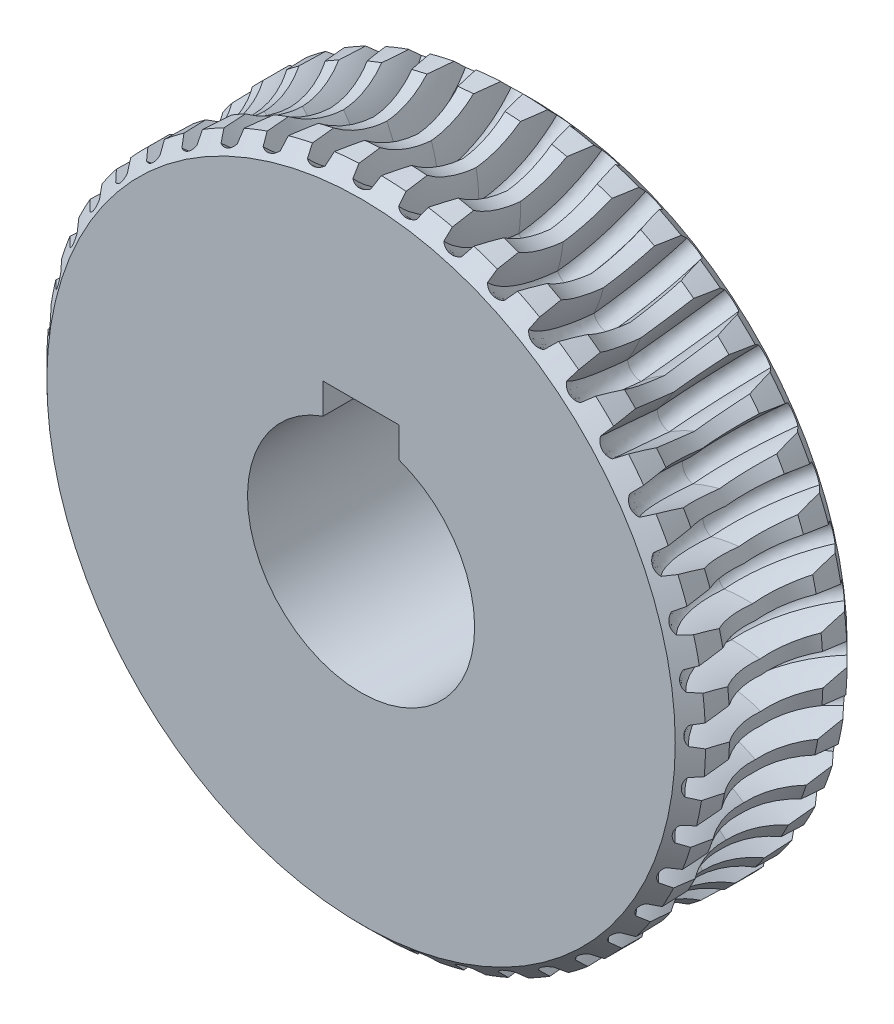
SolidWorks part; units mm, degrees
note: The reader was unsure of these and kept them because the rebuilt part matched: shared geometry of "Sketch4<2>".
ref_plane "Front Plane" through (0, 0, 0) normal (0, 0, 1) x (1, 0, 0)
ref_plane "Top Plane" through (0, 0, 0) normal (0, 1, 0) x (1, 0, 0)
ref_plane "Right Plane" through (0, 0, 0) normal (1, 0, 0) x (0, 0, -1)
sketch "Sketch1" plane through (0, 0, 0) normal (0, 0, 1) x (1, 0, 0)
  line L0 (0, 0) -> (0, 55.6872) construction
  line L2 (-5, 18.1421) -> (5, 18.1421)
  line L3 (-5, 18.1421) -> (-5, 14.1421)
  line L5 (5, 18.1421) -> (5, 14.1421)
  line L6 (-5, 18.1421) -> (0, 15) construction
  line L7 (0, 15) -> (5, 18.1421) construction
  circle A0 centre (0, 0) radius 43.5
  arc A1 (-5, 14.1421) -> (5, 14.1421) centre (0, 0) ccw
  point P4 (0, 15)
  dimension "D1" = 87
  dimension "D2" = 30
  dimension "D3" = 10
  dimension "D4" = 4
extrude "Boss-Extrude1" add sketch "Sketch1" along normal mid plane 22.7
chamfer "Chamfer1" distance 2 angle 45 2 edges at (43.5, 0, -11.35) (43.5, 0, 11.35)
sketch "Sketch2" plane through (0, 0, 0) normal (1, 0, 0) x (0, 0, -1)
  line L0 (0, 0) -> (0, -52) construction
  line L1 (0, 0) -> (54.4934, 0) construction
  circle A0 centre (0, -52) radius 10.5
  dimension "D2" = 21
  dimension "D1" = 52
revolve "Cut-Revolve1" cut sketch "Sketch2" angle 360 about L1
sketch "Sketch3" plane through (0, 0, 0) normal (1, 0, 0) x (0, 0, -1)
  circle A1 centre (0, -52) radius 10.5
  circle A2 centre (0, -52) radius 10.5
  dimension "D1" = 0
curve "Helix/Spiral1" pitch 6 height 1.5 turns 0.25
sketch "Sketch4" plane through (0, 0, 0) normal (0, 0, 1) x (1, 0, 0)
  line L0 (0, 0) -> (0, -56.2527) construction
  line L1 (3.45, -45.44) -> (-3.45, -45.44)
  line L2 (-3.45, -45.44) -> (-3.45, -44.44)
  line L3 (3.45, -45.44) -> (3.45, -44.44)
  arc A0 (-1.2018, -37.79) -> (1.2018, -37.79) centre (0, -39.13) cw
  arc A1 (-1.2018, -37.79) -> (-3.45, -44.44) centre (-19.0505, -35.4609) cw
  arc A2 (1.2018, -37.79) -> (3.45, -44.44) centre (19.0505, -35.4609) ccw
  dimension "D2" = 18
  dimension "D4" = 1.8
  dimension "D1" = 6.9
  dimension "D3" = 6.65
  dimension "D5" = 1.34
  dimension "D6" = 39.13
  dimension "D7" = 1
sweep "Cut-Sweep1" cut profiles "Sketch4" path "Helix/Spiral1"
sketch "Sketch5" plane through (0, 0, 0) normal (1, 0, 0) x (0, 0, -1)
  circle A1 centre (0, -52) radius 10.5
  circle A2 centre (0, -52) radius 10.5
  dimension "D1" = 0
curve "Helix/Spiral2" pitch 6 height 1.5 turns 0.25
sweep "Cut-Sweep2" cut profiles "Sketch4<2>" path "Helix/Spiral2"
sketch "Sketch4<2>" plane through (0, 0, 0) normal (0, 0, 1) x (1, 0, 0) same geometry as "Sketch4"
pattern_circular "CirPattern1" count 44 over 360 about axis through (0, 0, 11.35) along (0, 0, 1) of "Cut-Sweep2", "Cut-Sweep1"
ref_plane "Plane1" through (0, 0, 0) normal (1, 0, 0) x (0, 0, -1)
